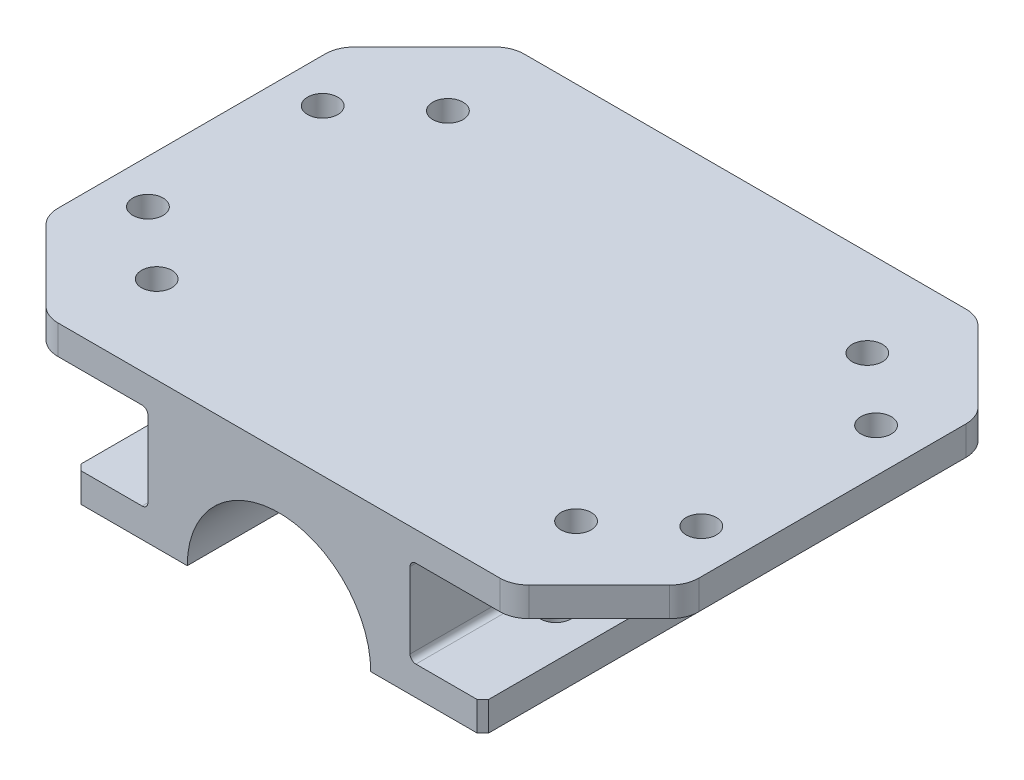
SolidWorks part; units mm, degrees
ref_plane "前视基准面" through (0, 0, 0) normal (0, 0, 1) x (1, 0, 0)
ref_plane "上视基准面" through (0, 0, 0) normal (0, 1, 0) x (1, 0, 0)
ref_plane "右视基准面" through (0, 0, 0) normal (1, 0, 0) x (0, 0, -1)
sketch "草图2" plane through (0, 0, 0) normal (0, 0, 1) x (1, 0, 0)
  line L0 (25, 0) -> (15.75, 0)
  line L1 (-25, 0) -> (-35, 0)
  line L2 (-35, 0) -> (-35, 5)
  line L3 (-35, 25) -> (35, 25)
  line L4 (0, 25) -> (0, 15.75) construction
  line L5 (25, 0) -> (35, 0)
  line L6 (35, 0) -> (35, 5)
  line L7 (-15.75, 0) -> (-25, 0)
  line L8 (-35, 25) -> (-55, 25)
  line L9 (-55, 25) -> (-55, 20)
  line L10 (-55, 20) -> (-35, 20)
  line L12 (-35, 5) -> (-22.5, 5)
  line L13 (-22.5, 5) -> (-22.5, 20)
  line L14 (-22.5, 20) -> (-35, 20)
  line L15 (22.5, 5) -> (22.5, 20)
  line L16 (22.5, 20) -> (35, 20)
  line L17 (35, 5) -> (22.5, 5)
  line L18 (55, 20) -> (35, 20)
  line L19 (55, 25) -> (55, 20)
  line L20 (35, 25) -> (55, 25)
  arc A0 (15.75, 0) -> (-15.75, 0) centre (0, 0) ccw
  dimension "D1" = 5
  dimension "D7" = 15.75
  dimension "D2" = 5
  dimension "D3" = 20
  dimension "D4" = 35
  dimension "D5" = 15
  dimension "D6" = 22.5
  dimension "D8" = 35
extrude "凸台-拉伸2" add sketch "草图2" along normal mid plane 80
fillet "圆角1" radius 1 4 edges at (22.5, 20, 0) (22.5, 5, 0) (-22.5, 20, 0) (-22.5, 5, 0)
sketch "草图3" plane through (0, 20, 0) normal (0, -1, 0) x (1, 0, 0)
  line L0 (-55, 40) -> (-55, 20) construction
  line L1 (-55, 40) -> (-55, -40) construction
  line L2 (-55, 20) -> (-27.5, 20) construction
  line L3 (0, 0) -> (0, 10) construction
  line L4 (0, 0) -> (10, 0) construction
  circle A0 centre (-27.5, 20) radius 2.6
  circle A1 centre (27.5, 20) radius 2.6
  circle A2 centre (27.5, -20) radius 2.6
  circle A3 centre (-27.5, -20) radius 2.6
extrude "切除-拉伸2" cut sketch "草图3" along normal blind 20
chamfer "倒角2" distance 1 angle 45 4 edges at (-35, 2.5, 40) (35, 2.5, 40) (-35, 2.5, -40) (35, 2.5, -40)
sketch "草图4" plane through (0, 25, 0) normal (0, 1, 0) x (1, 0, 0)
  line L0 (55, 0) -> (55, -25) construction
  line L1 (55, -40) -> (55, 40) construction
  line L2 (55, -25) -> (36, -25) construction
  line L3 (0, 0) -> (0, -10) construction
  line L4 (0, 0) -> (10, 0) construction
  circle A0 centre (36, -25) radius 2.6
  circle A1 centre (-36, -25) radius 2.6
  circle A2 centre (36, 25) radius 2.6
  circle A3 centre (-36, 25) radius 2.6
  dimension "D1" = 36
  dimension "D2" = 25
  dimension "D3" = 5.2
extrude "切除-拉伸3" cut sketch "草图4" against normal blind 10
sketch "草图5" plane through (0, 25, 0) normal (0, 1, 0) x (1, 0, 0)
  line L1 (-47.5, -15) -> (47.5, -15) construction
  line L2 (-47.5, -15) -> (-47.5, 15) construction
  line L3 (-47.5, 15) -> (47.5, 15) construction
  line L4 (47.5, -15) -> (47.5, 15) construction
  line L5 (-47.5, -15) -> (47.5, 15) construction
  line L6 (-47.5, 15) -> (47.5, -15) construction
  circle A0 centre (-47.5, 15) radius 2.6
  circle A1 centre (47.5, 15) radius 2.6
  circle A2 centre (47.5, -15) radius 2.6
  circle A3 centre (-47.5, -15) radius 2.6
  point P0 (0, 0)
  dimension "D1" = 30
  dimension "D2" = 95
extrude "切除-拉伸4" cut sketch "草图5" against normal blind 10
chamfer "倒角3" distance 15 angle 45 4 edges at (55, 22.5, -40) (55, 22.5, 40) (-55, 22.5, -40) (-55, 22.5, 40)
fillet "圆角2" radius 5 8 edges at (-55, 22.5, -25) (-40, 22.5, -40) (40, 22.5, -40) (55, 22.5, -25) (55, 22.5, 25) (40, 22.5, 40) (-40, 22.5, 40) (-55, 22.5, 25)
